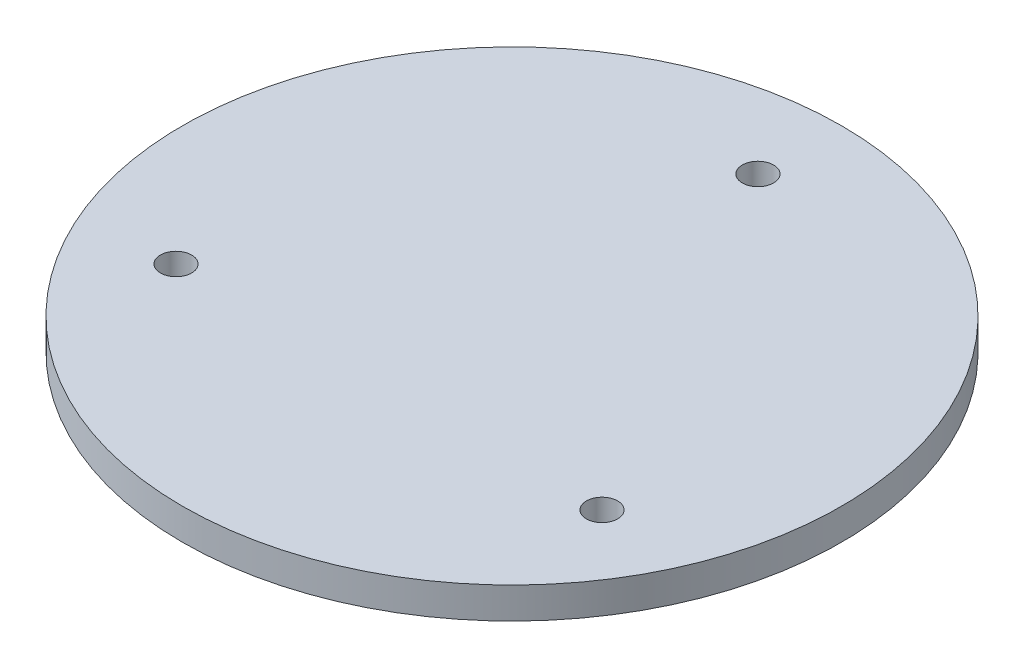
SolidWorks part; units mm, degrees
ref_plane "Front Plane" through (0, 0, 0) normal (0, 0, 1) x (1, 0, 0)
ref_plane "Top Plane" through (0, 0, 0) normal (0, 1, 0) x (1, 0, 0)
ref_plane "Right Plane" through (0, 0, 0) normal (1, 0, 0) x (0, 0, -1)
sketch "Sketch1" plane through (0, 0, 0) normal (0, 1, 0) x (1, 0, 0)
  circle A0 centre (0, 0) radius 134
  circle A1 centre (0, 100) radius 6.35
  circle A4 centre (86.6025, -50) radius 6.35
  circle A5 centre (-86.6025, -50) radius 6.35
  point P11 (0, 0)
  dimension "D1" = 268
  dimension "D2" = 12.7
  dimension "D3" = 100
  dimension "D4" = 3
extrude "Boss-Extrude1" add sketch "Sketch1" along normal blind 12.7
